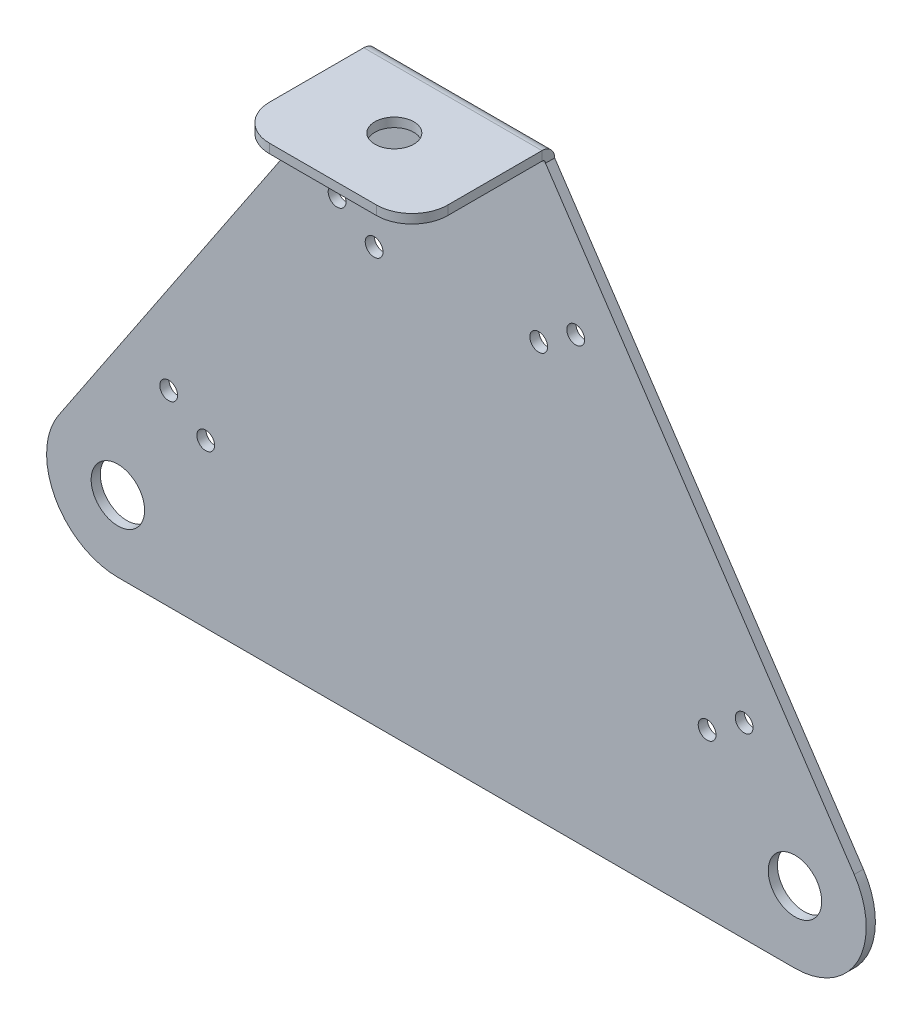
SolidWorks part; units mm, degrees
note: The reader was unsure of these and kept them because the rebuilt part matched: flange length of "Edge-Flange1".
material "6061 Alloy"
ref_plane "Front Plane" through (0, 0, 0) normal (0, 0, 1) x (1, 0, 0)
ref_plane "Top Plane" through (0, 0, 0) normal (0, 1, 0) x (1, 0, 0)
ref_plane "Right Plane" through (0, 0, 0) normal (1, 0, 0) x (0, 0, -1)
sketch "s" plane through (0, 0, 0) normal (0, 0, 1) x (1, 0, 0)
  line L0 (0, -4.0494) -> (0, -50004.0494) construction
  line L1 (0, 0) -> (-120.65, -208.9719) construction
  line L2 (-120.65, -208.9719) -> (0, -208.9719) construction
  line L3 (31.75, -30.356) -> (-31.75, -30.356)
  line L4 (-31.75, -30.356) -> (-141.7633, -194.8515)
  line L5 (-120.65, -234.3719) -> (120.65, -234.3719)
  line L6 (0, -234.3719) -> (0, -30.356) construction
  line L8 (31.75, -30.356) -> (141.7633, -194.8515)
  circle A0 centre (0, 0) radius 19.8437 construction
  circle A1 centre (-120.65, -208.9719) radius 9.525
  arc A2 (-141.7633, -194.8515) -> (-120.65, -234.3719) centre (-120.65, -208.9719) ccw
  circle A3 centre (120.65, -208.9719) radius 9.525
  arc A4 (141.7633, -194.8515) -> (120.65, -234.3719) centre (120.65, -208.9719) cw
  dimension "D1" = 39.6875
  dimension "D4" = 19.05
  dimension "D5" = 15.875
  dimension "D2" = 241.3
  dimension "D3" = 30
  dimension "D6" = 31.75
  dimension "D8" = 30.356
base flange "Base-Flange1" sketch "s" thickness 3.2639 reverse thickness direction no parameters "D1"=1.27
sketch "Sketch13" plane through (0, 0, 0) normal (0, 0, 1) x (1, 0, 0)
  line L0 (-120.65, -208.9719) -> (19.1089, 0)
  line L1 (120.65, -208.9719) -> (-19.1089, 0)
  line L2 (-102.5371, -167.6109) -> (-89.3413, -176.4362)
  line L3 (-42.5252, -77.8793) -> (-29.3294, -86.7045)
  line L4 (29.3294, -86.7045) -> (42.5252, -77.8793)
  line L5 (89.3413, -176.4362) -> (102.5371, -167.6109)
  line L6 (31.75, -30.356) -> (141.7633, -194.8515) construction
  line L7 (-31.75, -30.356) -> (-141.7633, -194.8515) construction
  line L8 (-120.65, -234.3719) -> (120.65, -234.3719) construction
  point P17 (-95.9392, -172.0236)
  point P18 (-35.9273, -82.2919)
  point P19 (35.9273, -82.2919)
  point P20 (95.9392, -172.0236)
  dimension "D1" = 44.45
  dimension "D2" = 152.4
  dimension "D3" = 15.875
  dimension "D4" = 57.9357
  dimension "D5" = 66.761
  dimension "D6" = 147.6674
  dimension "D7" = 156.4927
hole_wizard "1/4 (0.2500) Dowel Hole2" positions "Sketch14" profile "Sketch15" hole size "1/4" standard "ANSI Inch" end condition through all
sketch "Sketch14" plane through (0, 0, 0) normal (0, 0, 1) x (1, 0, 0)
  point P0 (-102.5371, -167.6109)
  point P3 (-89.3413, -176.4362)
  point P5 (-42.5252, -77.8793)
  point P8 (-29.3294, -86.7045)
  point P11 (29.3294, -86.7045)
  point P14 (42.5252, -77.8793)
  point P17 (89.3413, -176.4362)
  point P20 (102.5371, -167.6109)
sketch "Sketch15" plane through (-102.5371, -167.6109, 0) normal (1, 0, 0) x (0, -1, 0)
  line L0 (0, 0) -> (0, 3.2639)
  line L1 (0, 3.2639) -> (3.175, 3.2639)
  line L2 (3.175, 3.2639) -> (3.175, 0)
  line L5 (3.175, 0) -> (0, 0)
  line L11 (0, -6.35) -> (0, 107.95) construction
  dimension "Thru Hole Dia." = 6.35
  dimension "Thru Hole Depth" = 3.2639
edge flange "Edge-Flange1" sketch "Sketch18" flange angle 90 flange length 50.8 flange position bend outside bend radius 1.27 thickness 3.2639 relief rectangular parameters "D6"=10
sketch "Sketch18" plane through (0, -30.356, 0) normal (0, 1, 0) x (-1, 0, 0)
  line L0 (-31.75, 0) -> (31.75, 0) construction
  line L1 (-31.75, 0) -> (31.75, 0)
  line L2 (-31.75, 0) -> (-31.75, 47.5361)
  line L3 (-31.75, 47.5361) -> (31.75, 47.5361)
  line L4 (31.75, 47.5361) -> (31.75, 0)
bend "EdgeBend1" bend radius 1.27 bend angle 90 parameters "D5"=1
sketch "Sketch19" plane through (0, -25.8221, 0) normal (0, 1, 0) x (1, 0, 0)
  line L0 (141.7633, 3.2639) -> (31.75, 3.2639) construction
  point P0 (0, -22.1361)
  dimension "D1" = 25.4
hole_wizard "1/2 Clearance Hole1" positions "Sketch20" profile "Sketch21" hole size "1/2" standard "ANSI Inch" end condition up to next
sketch "Sketch20" plane through (0, -25.8221, 0) normal (0, 1, 0) x (1, 0, 0)
  point P0 (0, -22.1361)
sketch "Sketch21" plane through (0, -25.8221, 22.1361) normal (1, 0, 0) x (0, 0, 1)
  line L0 (0, 0) -> (0, 3.2639)
  line L1 (0, 3.2639) -> (6.9456, 3.2639)
  line L2 (6.9456, 3.2639) -> (6.9456, 0)
  line L5 (6.9456, 0) -> (0, 0)
  line L11 (0, -6.35) -> (0, 107.95) construction
  dimension "Thru Hole Dia." = 13.8913
  dimension "Thru Hole Depth" = 3.2639
fillet "Fillet1" radius 12.7 2 edges at (-31.75, -27.4541, 47.5361) (31.75, -27.4541, 47.5361)
sketch "Bend-Lines1" [suppressed] plane through (0, 0, 0) normal (0, 1, 0) x (1, 0, 0)
sketch "Bounding-Box1" [suppressed] plane through (0, 0, 0) normal (0, 1, 0) x (1, 0, 0)
sheet metal parameters "Sheet-Metal1" thickness 3.2639 parameters "D1"=1.27
flat pattern "Flat-Pattern1" [suppressed]
sketch "Bend-Lines2" plane through (0, 0, 0) normal (0, 1, 0) x (1, 0, 0)
sketch3d "Bounding-Box2" [suppressed]
  line L0 (-22.225, 241.5157, 0) -> (263.525, 241.5157, 0) construction
  line L1 (-22.225, -22.225, 0) -> (263.525, -22.225, 0) construction
  line L2 (-22.225, 241.5157, 0) -> (-22.225, -22.225, 0) construction
  line L3 (263.525, 241.5157, 0) -> (263.525, -22.225, 0) construction
sheet metal parameters "Sheet-Metal4" thickness 3.2639 parameters "D1"=1.27
flat pattern "Flat-Pattern1"
sketch "Bend-Lines2" plane through (0, 0, 0) normal (0, 0, 1) x (1, 0, 0)
sketch3d "Bounding-Box2" [suppressed]
  line L0 (-25.4, -25.4, 0) -> (266.7, -25.4, 0) construction
  line L1 (-25.4, 160.7119, 0) -> (266.7, 160.7119, 0) construction
  line L2 (-25.4, -25.4, 0) -> (-25.4, 160.7119, 0) construction
  line L3 (266.7, -25.4, 0) -> (266.7, 160.7119, 0) construction
sheet metal parameters "Sheet-Metal6" thickness 3.2639 parameters "D1"=1.27
flat pattern "Flat-Pattern1"
sketch "Bend-Lines2" plane through (0, 0, 0) normal (0, 0, 1) x (1, 0, 0)
  line L0 (31.75, -45.9808) -> (-31.75, -45.9808) construction
  line L1 (31.75, -45.9808) -> (-31.75, -45.9808) construction
sketch3d "Bounding-Box2" [suppressed]
  line L0 (-25.4, -25.4, 0) -> (266.7, -25.4, 0) construction
  line L1 (-25.4, 211.5364, 0) -> (266.7, 211.5364, 0) construction
  line L2 (-25.4, -25.4, 0) -> (-25.4, 211.5364, 0) construction
  line L3 (266.7, -25.4, 0) -> (266.7, 211.5364, 0) construction
bend of the flat pattern "Flatten-<EdgeBend1>1"
sheet metal parameters "Sheet-Metal7" thickness 3.2639 parameters "D1"=1.27
flat pattern "Flat-Pattern1" [suppressed]
sketch "Bend-Lines2" plane through (0, 0, 0) normal (0, 0, 1) x (1, 0, 0)
  line L0 (31.75, -28.0769) -> (-31.75, -28.0769) construction
  line L1 (31.75, -28.0769) -> (-31.75, -28.0769) construction
sketch3d "Bounding-Box2" [suppressed]
  line L0 (-25.4, 229.4404, 0) -> (266.7, 229.4404, 0) construction
  line L1 (-25.4, -25.4, 0) -> (266.7, -25.4, 0) construction
  line L2 (-25.4, 229.4404, 0) -> (-25.4, -25.4, 0) construction
  line L3 (266.7, 229.4404, 0) -> (266.7, -25.4, 0) construction
bend of the flat pattern "Flatten-<EdgeBend1>1"
sketch "Sketch19-1" plane through (0, -27.0677, -3.2639) normal (0, 0, -1) x (1, 0, 0)
  line L0 (141.7633, 167.7838) -> (31.75, 3.2884) construction
  point P0 (0, -22.1361)
  dimension "D1" = 12.2576
